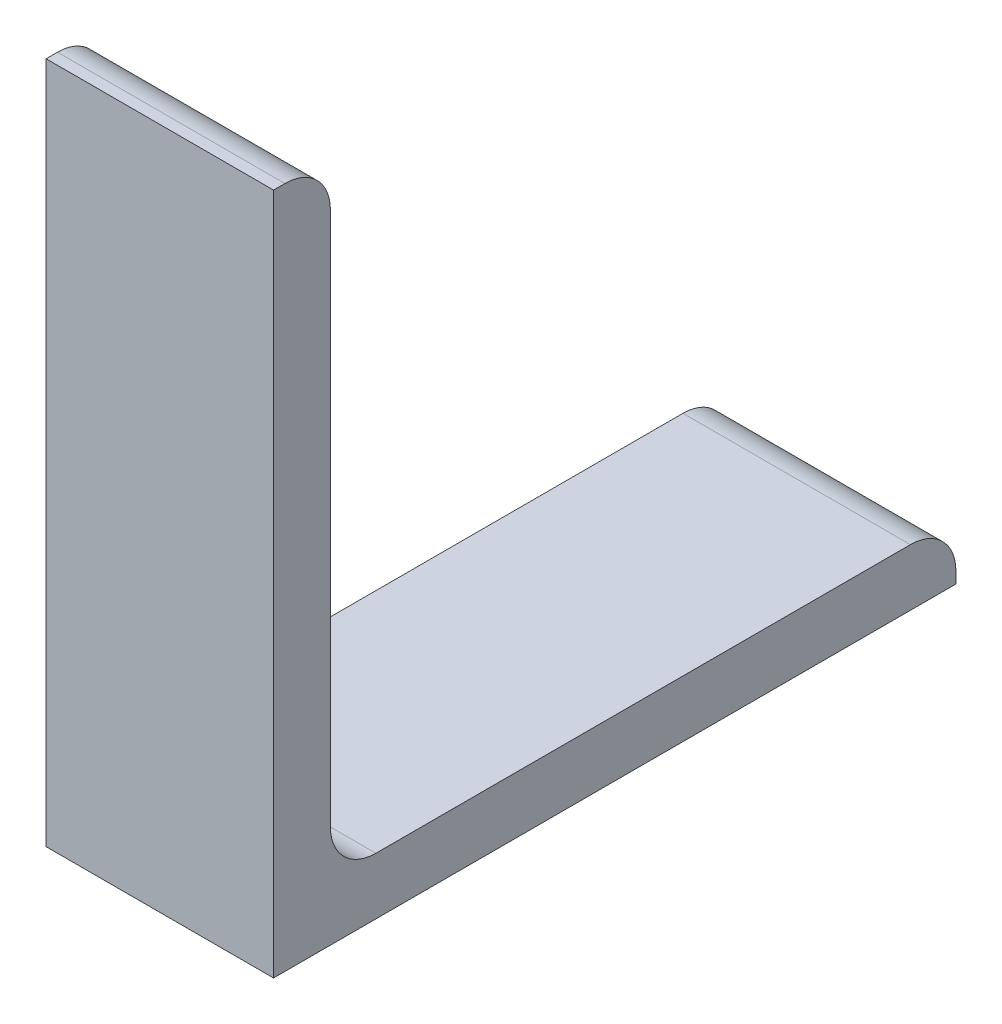
SolidWorks part; units mm, degrees
material "6061-T6 (SS)"
ref_plane "Front Plane" through (0, 0, 0) normal (0, 0, 1) x (1, 0, 0)
ref_plane "Top Plane" through (0, 0, 0) normal (0, 1, 0) x (1, 0, 0)
ref_plane "Right Plane" through (0, 0, 0) normal (1, 0, 0) x (0, 0, -1)
sketch "Sketch1" plane through (0, 0, 0) normal (1, 0, 0) x (0, 0, -1)
  line L0 (0, 76.2) -> (0, 0)
  line L1 (0, 0) -> (76.2, 0)
  line L2 (6.35, 71.12) -> (6.35, 11.43)
  line L3 (11.43, 6.35) -> (71.12, 6.35)
  line L4 (0, 76.2) -> (1.27, 76.2)
  line L5 (76.2, 1.27) -> (76.2, 0)
  line L6 (6.35, 76.2) -> (6.35, 6.35) construction
  line L7 (6.35, 6.35) -> (76.2, 6.35) construction
  arc A0 (6.35, 11.43) -> (11.43, 6.35) centre (11.43, 11.43) ccw
  arc A1 (71.12, 6.35) -> (76.2, 1.27) centre (71.12, 1.27) cw
  arc A2 (6.35, 71.12) -> (1.27, 76.2) centre (1.27, 71.12) ccw
  dimension "D1" = 76.2
  dimension "D3" = 5.08
  dimension "D2" = 6.35
extrude "Boss-Extrude1" add sketch "Sketch1" along normal blind 12.7 and the other way blind 12.7
